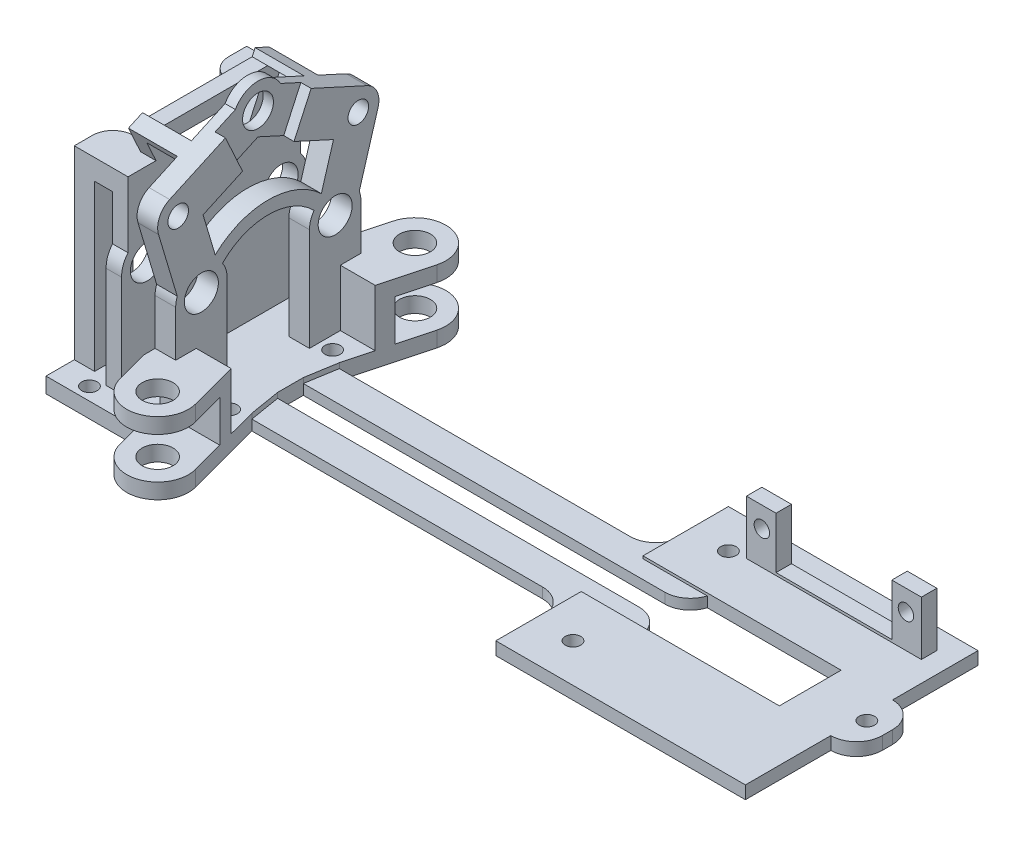
SolidWorks part; units mm, degrees
ref_plane "Front Plane" through (0, 0, 0) normal (0, 0, 1) x (1, 0, 0)
ref_plane "Top Plane" through (0, 0, 0) normal (0, 1, 0) x (1, 0, 0)
ref_plane "Right Plane" through (0, 0, 0) normal (1, 0, 0) x (0, 0, -1)
sketch "Sketch1" plane through (0, 0, 0) normal (0, 1, 0) x (1, 0, 0)
  line L6 (-24.1866, -2.5) -> (-24.1866, 2.5)
  line L7 (46.0437, 2.5) -> (-24.1866, 2.5)
  line L8 (46.0437, -2.5) -> (-24.1866, -2.5)
  line L9 (76.8134, 6) -> (76.8134, -6)
  line L10 (76.8134, -6) -> (50.8134, -6)
  line L11 (50.8134, 6) -> (76.8134, 6)
  line L12 (-24.1866, 0) -> (-39, 0) construction
  line L48 (86.8134, -22.6) -> (86.8134, -6)
  line L49 (91.8134, -1) -> (91.8134, 1)
  line L50 (86.8134, 6) -> (86.8134, 22.6)
  line L51 (86.8134, 22.6) -> (38.3134, 22.6)
  line L52 (38.3134, 22.6) -> (38.3134, 13.5)
  line L53 (33.3134, 8.5) -> (-23.1909, 8.5)
  line L54 (-23.1909, 8.5) -> (-19.2027, 23.4538)
  line L55 (-30.7973, 26.5462) -> (-31.9432, 22.25)
  line L56 (-31.9432, 22.25) -> (-49.4432, 22.25)
  line L57 (-49.4432, 22.25) -> (-49.4432, 9.25)
  line L58 (-49.4432, 9.25) -> (-45.5, 9.25)
  line L59 (-45.5, 9.25) -> (-45.5, 11.25)
  line L60 (-45.5, 11.25) -> (-42, 11.25)
  line L61 (-42, 11.25) -> (-42, -11.25)
  line L62 (-42, -11.25) -> (-45.5, -11.25)
  line L63 (-45.5, -11.25) -> (-45.5, -9.25)
  line L64 (-45.5, -9.25) -> (-49.4432, -9.25)
  line L65 (-49.4432, -9.25) -> (-49.4432, -22.25)
  line L66 (-49.4432, -22.25) -> (-31.9432, -22.25)
  line L67 (-31.9432, -22.25) -> (-30.7973, -26.5462)
  line L68 (-19.2027, -23.4538) -> (-23.1909, -8.5)
  line L69 (-23.1909, -8.5) -> (33.3134, -8.5)
  line L70 (38.3134, -13.5) -> (38.3134, -22.6)
  line L71 (38.3134, -22.6) -> (86.8134, -22.6)
  circle A0 centre (-26, -10) radius 1.5
  arc A12 (86.8134, -6) -> (91.8134, -1) centre (86.8134, -1) ccw
  arc A13 (91.8134, 1) -> (86.8134, 6) centre (86.8134, 1) ccw
  arc A14 (33.3134, 8.5) -> (38.3134, 13.5) centre (33.3134, 13.5) ccw
  arc A15 (-19.2027, 23.4538) -> (-30.7973, 26.5462) centre (-25, 25) ccw
  arc A16 (-30.7973, -26.5462) -> (-19.2027, -23.4538) centre (-25, -25) ccw
  arc A17 (38.3134, -13.5) -> (33.3134, -8.5) centre (33.3134, -13.5) ccw
  arc A23 (46.0437, 2.5) -> (50.8134, 6) centre (46.0437, 7.5) ccw
  arc A24 (50.8134, -6) -> (46.0437, -2.5) centre (46.0437, -7.5) ccw
  circle A25 centre (87.8134, 0) radius 1.5
  circle A26 centre (45.8134, -15.1) radius 1.5
  circle A27 centre (45.8134, 15.1) radius 1.5
  circle A28 centre (-43.5, 19.75) radius 1.5
  circle A29 centre (-43.5, -19.75) radius 1.5
  circle A30 centre (-25, 25) radius 3
  circle A31 centre (-26, 10) radius 1.5
  circle A33 centre (-25, -25) radius 3
  point P59 (0, 0)
  point P62 (0, 0)
  dimension "D1" = 17
  dimension "D2" = 45.2
  dimension "D3" = 44.5
  dimension "D4" = 10
  dimension "D5" = 13
  dimension "D6" = 3
  dimension "D7" = 17.5
  dimension "D8" = 3.5
ref_plane "Plane1" through (0, 2.5, 0) normal (0, 1, 0) x (1, 0, 0)
extrude "Boss-Extrude1" add sketch "Sketch1" along normal blind 2
sketch "Sketch2" plane through (0, 2.5, 0) normal (0, 1, 0) x (1, 0, 0)
  line L0 (77.0634, 18.6) -> (77.0634, 15.6)
  line L1 (54.5634, 18.6) -> (54.5634, 15.6)
  line L2 (82.8134, 15.6) -> (82.8134, 18.6)
  line L3 (48.8134, 15.6) -> (48.8134, 18.6)
  line L4 (91.8134, -1) -> (91.8134, 1)
  line L5 (86.8134, 6) -> (86.8134, 22.6)
  line L6 (86.8134, 22.6) -> (38.3134, 22.6)
  line L7 (38.3134, 22.6) -> (38.3134, 6)
  line L8 (38.3134, 6) -> (76.8134, 6)
  line L9 (76.8134, 6) -> (76.8134, -6)
  line L10 (76.8134, -6) -> (38.3134, -6)
  line L11 (38.3134, -6) -> (38.3134, -22.6)
  line L12 (38.3134, -22.6) -> (86.8134, -22.6)
  line L13 (86.8134, -22.6) -> (86.8134, -6)
  line L14 (82.8134, 18.6) -> (48.8134, 18.6)
  line L15 (82.8134, 15.6) -> (48.8134, 15.6)
  line L18 (38.3134, -22.6) -> (86.8134, -22.6) construction
  line L19 (38.3134, -13.5) -> (38.3134, -22.6) construction
  arc A0 (91.8134, 1) -> (86.8134, 6) centre (86.8134, 1) ccw
  arc A1 (86.8134, -6) -> (91.8134, -1) centre (86.8134, -1) ccw
  circle A2 centre (87.8134, 0) radius 1.5
  circle A3 centre (45.8134, -15.1) radius 1.5
  circle A4 centre (45.8134, 15.1) radius 1.5
  point P28 (0, 0)
  point P29 (0, 0)
  point P30 (0, 0)
  point P31 (76.8134, 0)
  point P34 (0, 0)
  point P35 (91.8134, 0)
  point P38 (0, 0)
  point P39 (0, 0)
  dimension "D12" = 7.5
  dimension "D14" = 5
  dimension "D15" = 5
  dimension "D23" = 3
  dimension "D24" = 3
  dimension "D25" = 3
  dimension "D1" = 16.6
  dimension "D2" = 16.6
  dimension "D3" = 4
  dimension "D4" = 34
  dimension "D5" = 3
  dimension "D6" = 3
  dimension "D7" = 7.5
  dimension "D8" = 4
  dimension "D9" = 45.2
  dimension "D10" = 48.5
  dimension "D11" = 48.5
  dimension "D13" = 7.5
  dimension "D16" = 2
  dimension "D17" = 5
  dimension "D18" = 5
  dimension "D19" = 5.75
  dimension "D20" = 22.5
  dimension "D21" = 4
  dimension "D22" = 11
  dimension "D26" = 5
extrude "Boss-Extrude2" add sketch "Sketch2" against normal up to surface (0.5 mm away) contours L13 A1 L4 A0 L5 L6 L7 L8 L9 L10 L11 L12 A4 A3 A2 L2 L15 L3 L14 | L15 L1 L14 L3 | L15 L0 L14 L1 | L15 L2 L14 L0 region at (79.9384, 2.5, -17.1) region at (65.8134, 2.5, -17.1) region at (51.6884, 2.5, -17.1) region at (89.8536, 2.5, 4.0403) up to face at (-26, 2, 8.5)
ref_plane "Plane2" through (0, 0, -15.6) normal (0, 0, 1) x (1, 0, 0)
sketch "Sketch3" plane through (0, 0, -15.6) normal (0, 0, 1) x (1, 0, 0)
  line L0 (48.8134, 2.5) -> (48.8134, 13)
  line L1 (48.8134, 13) -> (54.5634, 13)
  line L2 (54.5634, 13) -> (54.5634, 3)
  line L3 (54.5634, 3) -> (77.0634, 3)
  line L4 (77.0634, 3) -> (77.0634, 13)
  line L5 (77.0634, 13) -> (82.8134, 13)
  line L6 (82.8134, 13) -> (82.8134, 2.5)
  line L8 (82.8134, 2.5) -> (48.8134, 2.5)
  line L9 (65.8134, 2.5) -> (65.8134, 3) construction
  circle A0 centre (51.8134, 9) radius 1.5
  circle A1 centre (79.8134, 9) radius 1.5
  dimension "D1" = 3
  dimension "D2" = 4
  dimension "D3" = 3
  dimension "D4" = 10.5
  dimension "D5" = 0.5
extrude "Boss-Extrude3" add sketch "Sketch3" against normal blind 3
ref_plane "Plane3" through (-28.5, 0, 0) normal (1, 0, 0) x (0, 0, -1)
sketch "Sketch5" plane through (-28.5, 0, 0) normal (1, 0, 0) x (0, 0, -1)
  line L0 (2.5, 2) -> (-2.5, 2) construction
  circle A0 centre (0, 46) radius 9
  circle A3 centre (0, 46) radius 2.5
  circle A4 centre (-17.5, 38) radius 2.1
  circle A5 centre (17.5, 38) radius 2.1
  point P10 (0, 0)
  dimension "D5" = 4.2
  dimension "D6" = 4.2
  dimension "D7" = 5
  dimension "D9" = 18
  dimension "D1" = 17.5
  dimension "D2" = 17.5
  dimension "D3" = 8
  dimension "D4" = 8
  dimension "D8" = 44
sketch "Sketch6" plane through (0, 2, 0) normal (0, 1, 0) x (1, 0, 0)
  line L0 (-31.9432, 22.25) -> (-49.4432, 22.25) construction
  line L1 (-30.7973, 26.5462) -> (-31.9432, 22.25) construction
  line L2 (-23.1909, 8.5) -> (-19.2027, 23.4538) construction
  line L3 (-49.4432, -22.25) -> (-31.9432, -22.25) construction
  line L4 (-31.9432, -22.25) -> (-30.7973, -26.5462) construction
  line L5 (-19.2027, -23.4538) -> (-23.1909, -8.5) construction
  line L6 (-31.9432, 22.25) -> (-49.4432, 22.25)
  line L7 (-30.7973, 26.5462) -> (-31.9432, 22.25)
  line L8 (-23.1909, 8.5) -> (-19.2027, 23.4538)
  line L9 (-49.4432, -22.25) -> (-31.9432, -22.25)
  line L10 (-31.9432, -22.25) -> (-30.7973, -26.5462)
  line L11 (-19.2027, -23.4538) -> (-23.1909, -8.5)
  line L12 (-49.4432, -9.25) -> (-49.4432, -22.25) construction
  line L13 (-45.5, -11.25) -> (-45.5, -9.25) construction
  line L14 (-45.5, -9.25) -> (-49.4432, -9.25) construction
  line L15 (-42, -11.25) -> (-45.5, -11.25) construction
  line L16 (-42, 11.25) -> (-42, -11.25) construction
  line L17 (-45.5, 9.25) -> (-45.5, 11.25) construction
  line L18 (-45.5, 11.25) -> (-42, 11.25) construction
  line L19 (-49.4432, 9.25) -> (-45.5, 9.25) construction
  line L20 (-49.4432, 22.25) -> (-49.4432, 9.25) construction
  line L21 (-49.4432, -9.25) -> (-49.4432, -22.25)
  line L22 (-45.5, -11.25) -> (-45.5, -9.25)
  line L23 (-45.5, -9.25) -> (-49.4432, -9.25)
  line L24 (-42, -11.25) -> (-45.5, -11.25)
  line L25 (-42, 11.25) -> (-42, -11.25)
  line L26 (-45.5, 9.25) -> (-45.5, 11.25)
  line L27 (-45.5, 11.25) -> (-42, 11.25)
  line L28 (-49.4432, 9.25) -> (-45.5, 9.25)
  line L29 (-49.4432, 22.25) -> (-49.4432, 9.25)
  line L30 (-23.1909, 8.5) -> (-24.1866, 2.5)
  line L31 (-24.1866, 2.5) -> (-24.1866, -2.5)
  line L32 (-24.1866, -2.5) -> (-23.1909, -8.5)
  arc A0 (-19.2027, 23.4538) -> (-30.7973, 26.5462) centre (-25, 25) ccw construction
  arc A1 (-30.7973, -26.5462) -> (-19.2027, -23.4538) centre (-25, -25) ccw construction
  arc A2 (-19.2027, 23.4538) -> (-30.7973, 26.5462) centre (-25, 25) ccw
  arc A3 (-30.7973, -26.5462) -> (-19.2027, -23.4538) centre (-25, -25) ccw
  circle A4 centre (-25, -25) radius 3 construction
  circle A5 centre (-25, 25) radius 3 construction
  circle A6 centre (-43.5, 19.75) radius 1.5 construction
  circle A7 centre (-26, 10) radius 1.5 construction
  circle A9 centre (-43.5, -19.75) radius 1.5 construction
  circle A10 centre (-25, -25) radius 3
  circle A11 centre (-25, 25) radius 3
  circle A12 centre (-43.5, 19.75) radius 1.5
  circle A13 centre (-26, 10) radius 1.5
  circle A15 centre (-43.5, -19.75) radius 1.5
  circle A17 centre (-26, -10) radius 1.5 construction
  circle A18 centre (-26, -10) radius 1.5
extrude "Boss-Extrude4" add sketch "Sketch6" along normal blind 1
sketch "Sketch7" plane through (0, 3, 0) normal (0, 1, 0) x (1, 0, 0)
  line L0 (-24.1866, 0) -> (76.8134, 0) construction
  line L1 (-24.1866, -2.5) -> (-24.1866, 2.5) construction
  line L2 (76.8134, 6) -> (76.8134, -6) construction
  line L3 (-25, -25) -> (-28.3462, -12.4538) construction
  line L4 (-30.7973, -26.5462) -> (-34.1435, -14)
  line L5 (-19.2027, -23.4538) -> (-22.5488, -10.9076)
  line L6 (-31.9432, -22.25) -> (-30.7973, -26.5462) construction
  line L7 (-21.7241, -14) -> (-38.146, -14)
  line L8 (-23.1909, -8.5) -> (33.3134, -8.5) construction
  line L9 (-25, 25) -> (-28.3462, 12.4538) construction
  line L10 (-30.7973, 26.5462) -> (-34.1435, 14)
  line L11 (-19.2027, 23.4538) -> (-22.5488, 10.9076)
  line L12 (-21.7241, 14) -> (-38.146, 14)
  line L13 (-32.5, -20.1623) -> (-32.5, -14)
  line L14 (-32.5, 20.1623) -> (-32.5, 14)
  circle A0 centre (-25, -25) radius 3 construction
  circle A1 centre (-25, -25) radius 3
  arc A2 (-30.7973, -26.5462) -> (-19.2027, -23.4538) centre (-25, -25) ccw
  arc A3 (-22.5488, -10.9076) -> (-34.1435, -14) centre (-28.3462, -12.4538) ccw
  arc A4 (-30.7973, -26.5462) -> (-19.2027, -23.4538) centre (-25, -25) ccw construction
  circle A5 centre (-25, 25) radius 3
  arc A6 (-30.7973, 26.5462) -> (-19.2027, 23.4538) centre (-25, 25) cw
  arc A7 (-22.5488, 10.9076) -> (-34.1435, 14) centre (-28.3462, 12.4538) cw
  point P9 (-26.6731, -18.7269)
  point P27 (-26.6731, 18.7269)
  circle M14 centre (-25, -25) radius 3
  line M15 (-30.7973, 26.5462) -> (-31.9432, 22.25)
  line M27 (-31.9432, -22.25) -> (-30.7973, -26.5462)
  arc M28 (-30.7973, -26.5462) -> (-19.2027, -23.4538) centre (-25, -25) ccw
  line M29 (-19.2027, -23.4538) -> (-23.1909, -8.5)
  arc M34 (-19.2027, 23.4538) -> (-30.7973, 26.5462) centre (-25, 25) ccw
  circle M35 centre (-25, 25) radius 3
  dimension "D1" = 5.5
  dimension "D2" = 7.5
extrude "Boss-Extrude5" add sketch "Sketch7" along normal blind 11 contours L7 L4 M29 M27 M28 M14 | L12 L11 L10 M34 M15 M35 region at (-26.0071, 3, 21.4837) region at (-26.0071, 3, -21.4837)
ref_plane "Plane4" through (-33.5, 0, 0) normal (1, 0, 0) x (0, 0, -1)
sketch "Sketch8" plane through (-33.5, 0, 0) normal (1, 0, 0) x (0, 0, -1)
  line L0 (0, 46) -> (0, 53.4818) construction
  circle A0 centre (0, 46) radius 9 construction
  circle A1 centre (0, 46) radius 9
  circle A2 centre (13, 22.9078) radius 13
  circle A3 centre (-13, 22.9078) radius 17.5
  circle A4 centre (-13, 22.9078) radius 13
  point P8 (0, 0)
  dimension "D1" = 35
  dimension "D2" = 26
  dimension "D3" = 13
sketch "Sketch9" plane through (-28.5, 0, 0) normal (1, 0, 0) x (0, 0, -1)
  line L0 (0, 41.6019) -> (0, 51) construction
  line L1 (-14, 3) -> (-8.5, 3) construction
  line L4 (14, 14) -> (14, 3) construction
  line L10 (-4.3915, 48.3906) -> (-19.163, 41.6379)
  line L12 (4.3915, 48.3906) -> (19.163, 41.6379)
  line L13 (0, 41.6019) -> (12.6721, 35.8089)
  line L14 (13, 22.9078) -> (17.5, 38) construction
  line L15 (13, 22.9078) -> (13, 3) construction
  line L16 (17.9964, 3) -> (7.9977, 3)
  line L17 (10.0245, 26.9295) -> (12.6721, 35.8089)
  line L18 (17.6884, 24.6349) -> (21.3138, 36.7937)
  line L19 (17.9964, 22.9078) -> (17.9964, 3)
  line L20 (7.9977, 22.9745) -> (7.9977, 3)
  line L21 (0, 41.6019) -> (-12.6721, 35.8089)
  line L22 (-13, 22.9078) -> (-13, 3) construction
  line L23 (-13, 22.9078) -> (-17.5, 38) construction
  line L24 (-7.9977, 22.9745) -> (-7.9977, 3)
  line L25 (-17.9964, 22.9078) -> (-17.9964, 3)
  line L26 (17.5, 38) -> (0, 46) construction
  line L27 (-17.6884, 24.6349) -> (-21.3138, 36.7937)
  line L28 (-10.0245, 26.9295) -> (-12.6721, 35.8089)
  line L29 (-17.9964, 3) -> (-7.9977, 3)
  line L30 (7.9977, 17) -> (-7.9977, 17) construction
  line L31 (11.25, 3) -> (-11.25, 3) construction
  circle A2 centre (0, 46) radius 3
  arc A7 (4.3915, 48.3906) -> (-4.3915, 48.3906) centre (0, 46) ccw
  arc A11 (17.6884, 24.6349) -> (17.9964, 22.9078) centre (13, 22.9078) cw
  arc A12 (19.163, 41.6379) -> (21.3138, 36.7937) centre (17.5, 38) cw
  arc A13 (7.9977, 22.9745) -> (10.0245, 26.9295) centre (13, 22.9078) cw
  circle A14 centre (17.5, 38) radius 2
  circle A15 centre (13, 22.9078) radius 3.2995
  circle A16 centre (-13, 22.9078) radius 3.2995
  circle A17 centre (-17.5, 38) radius 2
  arc A18 (-7.9977, 22.9745) -> (-10.0245, 26.9295) centre (-13, 22.9078) ccw
  arc A19 (-19.163, 41.6379) -> (-21.3138, 36.7937) centre (-17.5, 38) ccw
  arc A20 (-17.6884, 24.6349) -> (-17.9964, 22.9078) centre (-13, 22.9078) ccw
  arc A21 (8.9012, 25.7761) -> (-8.9012, 25.7761) centre (0, 17) ccw
  arc A22 (10.3119, 27.8933) -> (-10.3119, 27.8933) centre (0, 17) ccw
  point P2 (19.5011, 30.7143)
  point P29 (-12.6216, 12.8494)
  point P31 (-15.0608, 30.3494)
  point P43 (8.75, 42)
  point P44 (15.0608, 30.3494)
  point P45 (12.6216, 12.8494)
  point P46 (-8.75, 42)
  dimension "D2" = 9.9987
  dimension "D3" = 5
  dimension "D4" = 4.9964
  dimension "D5" = 6
  dimension "D6" = 4
  dimension "D7" = 5.0027
  dimension "D8" = 4.9964
  dimension "D13" = 8
  dimension "D15" = 15
  dimension "D9" = 4
  dimension "D10" = 6.5989
  dimension "D16" = 12.5
  dimension "D11" = 8
  dimension "D12" = 3.9995
  dimension "D14" = 4
  dimension "D17" = 14
extrude "Boss-Extrude6" add sketch "Sketch9" against normal blind 4 contours A13 L20 L16 L19 A11 L18 A12 L12 A7 L29 L13 L17 A14 A2 A15 | A13 L17 region at (-28.5, 50.3556, 0) region at (-28.5, 26.5486, 9.2618)
sketch "Sketch10" plane through (-28.5, 0, 0) normal (1, 0, 0) x (0, 0, -1)
  line L9 (0, 41.6019) -> (12.6721, 35.8089) construction
  line L11 (4.3915, 48.3906) -> (19.163, 41.6379) construction
  line L12 (0, 41.6019) -> (12.6721, 35.8089)
  line L13 (4.3915, 48.3906) -> (8.3261, 46.5919)
  line L14 (0, 41.6019) -> (0, 51) construction
  line L15 (8.3261, 46.5919) -> (5, 39.3161)
  line L16 (0, 41.6019) -> (-12.6721, 35.8089)
  line L17 (-8.3261, 46.5919) -> (-5, 39.3161)
  line L18 (-4.3915, 48.3906) -> (-8.3261, 46.5919)
  arc A2 (4.3915, 48.3906) -> (-4.3915, 48.3906) centre (0, 46) ccw construction
  arc A3 (4.3915, 48.3906) -> (-4.3915, 48.3906) centre (0, 46) ccw
  circle M8 centre (0, 46) radius 3
  line M13 (0, 41.6019) -> (12.6721, 35.8089)
  line M31 (19.163, 41.6379) -> (4.3915, 48.3906)
  arc M32 (4.3915, 48.3906) -> (-4.3915, 48.3906) centre (0, 46) ccw
  line M54 (-4.3915, 48.3906) -> (-19.163, 41.6379)
  dimension "D1" = 5
extrude "Cut-Extrude1" cut sketch "Sketch10" against normal blind 2 contours M8 M13 M31 M32 | L16 L14 A3 L17 M8 M54 region at (-28.5, 44.8609, -3.918) region at (-28.5, 44.8609, 3.918)
sketch "Sketch12" plane through (-42, 0, 0) normal (-1, 0, 0) x (0, 0, 1)
  line L0 (0, 51) -> (0, 0) construction
  line L1 (-13, 3) -> (-13, 22.9078) construction
  line L2 (-22.25, 3) -> (-9.25, 3) construction
  line L3 (-17.9964, 3) -> (-17.9964, 22.7177)
  line L4 (-8, 3) -> (-8, 22.9078)
  line L6 (-8, 3) -> (-17.9964, 3)
  line L7 (-17.9964, 22.9078) -> (-17.9964, 14) construction
  line L14 (-7.2582, 30.127) -> (-13.6686, 44.1497)
  line L15 (-4.3915, 48.3906) -> (-19.163, 41.6379) construction
  line L16 (-13.6686, 44.1497) -> (-10.9402, 45.3969)
  line L17 (-10.9402, 45.3969) -> (-10.37, 44.1497)
  line L18 (8.9985, 41.1497) -> (-8.9985, 41.1497)
  line L19 (10.37, 44.1497) -> (-10.37, 44.1497)
  line L20 (-8.9985, 41.1497) -> (-4.5, 31.3091)
  line L21 (8.9985, 41.1497) -> (4.5, 31.3091)
  line L22 (13, 3) -> (13, 22.9078) construction
  line L23 (10.9402, 45.3969) -> (10.37, 44.1497)
  line L24 (13.6686, 44.1497) -> (10.9402, 45.3969)
  line L25 (7.2582, 30.127) -> (13.6686, 44.1497)
  line L26 (8, 3) -> (17.9964, 3)
  line L27 (8, 3) -> (8, 22.9078)
  line L28 (17.9964, 3) -> (17.9964, 22.7177)
  line L29 (8, 3) -> (-8, 3)
  line L30 (-16.75, 39) -> (-16.75, 26.215)
  line L31 (-16.75, 39) -> (-11.3145, 39)
  line L32 (-9.25, 3) -> (-9.25, 0) construction
  line L33 (11.3145, 39) -> (16.75, 39)
  line L34 (16.75, 39) -> (16.75, 26.215)
  line L35 (9.25, 3) -> (9.25, 0) construction
  arc A0 (8.9012, 25.7761) -> (-8.9012, 25.7761) centre (0, 17) ccw construction
  arc A1 (10.3119, 27.8933) -> (-10.3119, 27.8933) centre (0, 17) ccw construction
  arc A2 (8.9031, 25.7741) -> (-8.9031, 25.7741) centre (0, 17) ccw
  arc A3 (4.5, 31.3091) -> (-4.5, 31.3091) centre (0, 17) ccw
  circle A4 centre (-13, 22.9078) radius 3.2995 construction
  circle A5 centre (-13, 22.9078) radius 3.2995
  arc A6 (4.3915, 48.3906) -> (-4.3915, 48.3906) centre (0, 46) ccw construction
  arc A8 (-8, 22.9078) -> (-8.9031, 25.7741) centre (-13, 22.9078) ccw
  arc A9 (-10.8077, 27.4016) -> (-17.9964, 22.7177) centre (-13, 22.9078) ccw
  arc A10 (-7.2582, 30.127) -> (-10.8077, 27.4016) centre (0, 17) ccw
  arc A11 (7.2582, 30.127) -> (10.8077, 27.4016) centre (0, 17) cw
  arc A12 (10.8077, 27.4016) -> (17.9964, 22.7177) centre (13, 22.9078) cw
  arc A13 (8, 22.9078) -> (8.9031, 25.7741) centre (13, 22.9078) cw
  circle A14 centre (13, 22.9078) radius 3.2995
  point P16 (-13, 12.9539)
  point P43 (0, 44.1497)
  point P44 (0, 41.1497)
  point P55 (13, 12.9539)
  line M33 (11.25, 3) -> (-11.25, 3)
  dimension "D1" = 5
  dimension "D2" = 3
  dimension "D3" = 3
  dimension "D4" = 4.5
  dimension "D5" = 7.5
  dimension "D6" = 36
  dimension "D7" = 7.5
extrude "Boss-Extrude7" add sketch "Sketch12" against normal blind 3 contours A13 L27 L26 L28 A12 A11 L25 L24 L23 L19 L17 L16 L14 A10 A9 L3 L6 L4 A8 A2 L21 A3 L20 L18 A5 A14 M33 | L27 A13 A2 A8 L4 M33 | A10 L14 L31 L30 A9 | A11 A12 L25 region at (-42, 12.8589, -17.4402) region at (-42, 32.9471, -12.9533) region at (-42, 15.8628, 0) region at (-42, 32.9471, 12.9533)
sketch "Sketch14" plane through (-39, 0, 0) normal (1, 0, 0) x (0, 0, -1)
  line L0 (10.37, 44.1497) -> (13.0984, 42.9024)
  line L1 (11.3145, 39) -> (13.6686, 44.1497) construction
  line L2 (13.0984, 42.9024) -> (13.6686, 44.1497)
  line L3 (13.6686, 44.1497) -> (10.9402, 45.3969)
  line L4 (10.9402, 45.3969) -> (10.37, 44.1497)
  line L5 (-10.37, 44.1497) -> (-13.0984, 42.9024)
  line L6 (-11.3145, 39) -> (-13.6686, 44.1497) construction
  line L7 (-13.0984, 42.9024) -> (-13.6686, 44.1497)
  line L8 (-13.6686, 44.1497) -> (-10.9402, 45.3969)
  line L9 (-10.9402, 45.3969) -> (-10.37, 44.1497)
extrude "Boss-Extrude9" add sketch "Sketch14" along normal up to surface (6.5 mm away) up to face at (-32.5, 23.7065, 0)
sketch "Sketch15" plane through (-28.5, 0, 0) normal (1, 0, 0) x (0, 0, -1)
  line L0 (-31, 14) -> (-31, 0) construction
  line L1 (-31, 3) -> (-17, 3)
  line L2 (-31, 3) -> (-31, 11)
  line L3 (-31, 11) -> (-17, 11)
  line L4 (-17, 3) -> (-17, 11)
  line L5 (-14, 14) -> (-14, 3) construction
  line L6 (-23.4538, 14) -> (-31, 14) construction
  line L8 (31, 0) -> (31, 14) construction
  line L9 (17, 3) -> (17, 11)
  line L10 (31, 11) -> (17, 11)
  line L11 (31, 3) -> (31, 11)
  line L12 (31, 3) -> (17, 3)
  line L13 (14, 3) -> (14, 14) construction
  line L14 (31, 14) -> (23.4538, 14) construction
  line L15 (23.4538, 0) -> (31, 0) construction
  dimension "D1" = 8
  dimension "D2" = 3
  dimension "D3" = 3
  dimension "D4" = 3
  dimension "D5" = 3
  dimension "D6" = 3
extrude "Cut-Extrude2" cut sketch "Sketch15" against normal up to surface (4 mm away) and the other way blind 20 up to face at (-32.5, 34.6226, 0)
sketch "Sketch16" plane through (0, 3, 0) normal (0, 1, 0) x (1, 0, 0)
  line L0 (-45.5, -11.25) -> (-45.5, -9.25) construction
  line L1 (-49.4432, 9.25) -> (-45.5, 9.25)
  line L2 (-49.4432, 9.25) -> (-49.4432, 16.75)
  line L3 (-49.4432, 16.75) -> (-45.5, 16.75)
  line L4 (-45.5, 9.25) -> (-45.5, 16.75)
  line L5 (-49.4432, -9.25) -> (-45.5, -9.25)
  line L6 (-49.4432, -9.25) -> (-49.4432, -16.75)
  line L7 (-49.4432, -16.75) -> (-45.5, -16.75)
  line L8 (-45.5, -9.25) -> (-45.5, -16.75)
  line L9 (-45.5, 9.25) -> (-45.5, 11.25) construction
  dimension "D1" = 7.5
extrude "Boss-Extrude10" add sketch "Sketch16" along normal blind 36
fillet "Fillet1" radius 4 2 edges at (-49.4432, 19.5, 9.25) (-49.4432, 19.5, -9.25)
sketch "Sketch17" plane through (-42, 0, 0) normal (-1, 0, 0) x (0, 0, 1)
  line L0 (-9.25, 39) -> (-9.25, 0) construction
  line L1 (-16.75, 39) -> (-9.25, 39)
  line L2 (-16.75, 39) -> (-16.75, 35)
  line L3 (-16.75, 35) -> (-9.25, 35)
  line L4 (-9.25, 39) -> (-9.25, 35)
  line L5 (16.75, 39) -> (9.25, 39)
  line L7 (16.75, 35) -> (9.25, 35)
  line L8 (9.25, 39) -> (9.25, 35)
  line L9 (9.25, 39) -> (9.25, 0) construction
  line L10 (16.75, 39) -> (16.75, 35)
  line L11 (16.75, 39) -> (16.75, 26.215) construction
  dimension "D1" = 4
extrude "Boss-Extrude11" add sketch "Sketch17" along normal up to surface (3.5 mm away) up to face at (-45.5, 14, -12.4167)
